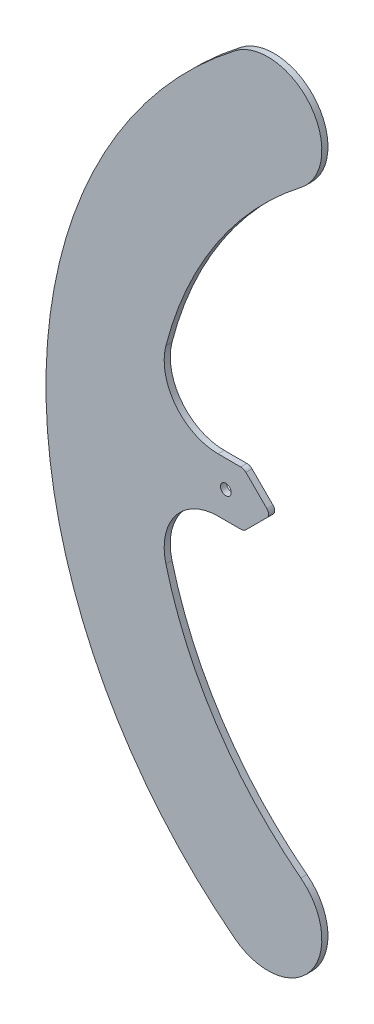
SolidWorks part; units mm, degrees
ref_plane "Front Plane" through (0, 0, 0) normal (0, 0, 1) x (1, 0, 0)
ref_plane "Top Plane" through (0, 0, 0) normal (0, 1, 0) x (1, 0, 0)
ref_plane "Right Plane" through (0, 0, 0) normal (1, 0, 0) x (0, 0, -1)
sketch "Sketch1" plane through (0, 0, 0) normal (0, 0, 1) x (1, 0, 0)
  line L0 (-32.8019, 0) -> (18.2589, 0) construction
  line L1 (70.5, 105) -> (70.5, 135) construction
  line L2 (205.5, -110) -> (-64.5, -110)
  line L3 (205.5, -110) -> (205.5, 110)
  line L4 (205.5, 110) -> (-64.5, 110)
  line L5 (-19.5, 7.5) -> (-19.5, -6)
  line L6 (-18, -7.5) -> (-9.5, -7.5)
  line L7 (-9.5, -7.5) -> (-3.0607, -1.0607)
  line L8 (-3.0607, 1.0607) -> (-9.5, 7.5)
  line L9 (-9.5, 7.5) -> (-19.5, 7.5)
  line L10 (-19.5, 7.5) -> (-19.5, -6)
  line L11 (-18, -7.5) -> (-9.5, -7.5)
  line L12 (-9.5, -7.5) -> (-3.0607, -1.0607)
  line L13 (-3.0607, 1.0607) -> (-9.5, 7.5)
  line L15 (-64.5, -110) -> (-64.5, 110)
  line L16 (205.5, -110) -> (-64.5, 110) construction
  line L17 (205.5, 110) -> (-64.5, -110) construction
  line L18 (-18, 7.5) -> (-34.2318, 7.5)
  line L19 (-18, -7.5) -> (-34.2318, -7.5)
  line L85 (-9.5, 7.5) -> (-19.5, 7.5)
  circle A0 centre (-14.5, 0) radius 1.5 construction
  arc A2 (-19.5, -6) -> (-18, -7.5) centre (-18, -6) ccw
  arc A4 (-19.5, -6) -> (-18, -7.5) centre (-18, -6) ccw
  circle A6 centre (-14.5, 0) radius 1.5
  circle A7 centre (-14.5, 0) radius 1.5
  circle A8 centre (70.5, 0) radius 135
  circle A9 centre (70.5, 0) radius 105
  circle A11 centre (-2.8144, 95) radius 15
  circle A12 centre (-2.8144, -95) radius 15
  arc A32 (-3.0607, -1.0607) -> (-3.0607, 1.0607) centre (-4.1213, 0) ccw
  arc A33 (-3.0607, -1.0607) -> (-3.0607, 1.0607) centre (-4.1213, 0) ccw
  point P19 (-64.5, 0)
  point P27 (70.5, 110)
  dimension "D3" = 270
  dimension "D5" = 30
  dimension "D2" = 55
  dimension "D4" = 220
  dimension "D1" = 0
extrude "Boss-Extrude1" add sketch "Sketch1" along normal blind 1.7 contours A11 | A8 A12 A9 A11 | A12 | L18 A9 L19 A4 L10 | L10 A4 L11 L12 L13 A6 region at (-2.8144, -95, 0) region at (-37.1858, 0, 0) region at (-2.8144, 95, 0) region at (-26.9388, -0.0154, 0) region at (-12.3896, 0.0175, 0)
fillet "Fillet1" radius 15 2 edges at (-34.2318, -7.5, 0.85) (-34.2318, 7.5, 0.85)
fillet "Fillet2" radius 2 2 edges at (-9.5, -7.5, 0.85) (-9.5, 7.5, 0.85)
